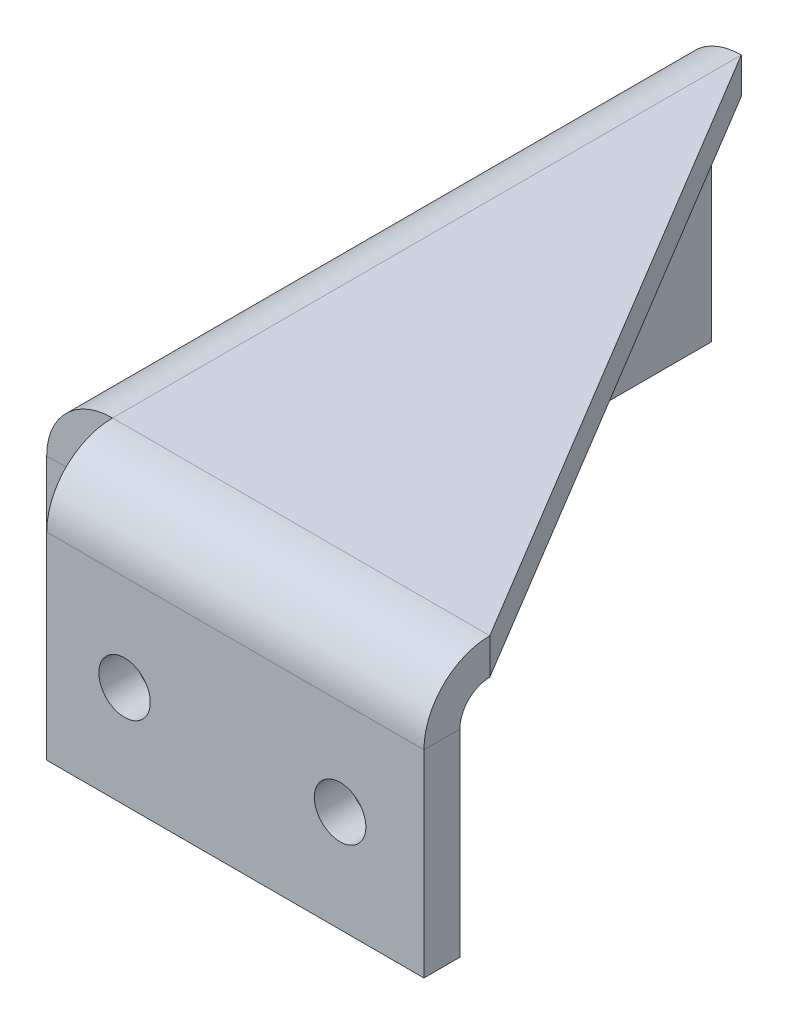
SolidWorks part; units mm, degrees
note: The reader was unsure of these and kept them because the rebuilt part matched: flange length of "Edge-Flange1", "Edge-Flange2".
material "1060 Alloy"
ref_plane "Front Plane" through (0, 0, 0) normal (0, 0, 1) x (1, 0, 0)
ref_plane "Top Plane" through (0, 0, 0) normal (0, 1, 0) x (1, 0, 0)
ref_plane "Right Plane" through (0, 0, 0) normal (1, 0, 0) x (0, 0, -1)
sketch "Sketch1" plane through (0, 0, 0) normal (0, 1, 0) x (1, 0, 0)
  line L1 (0, 0) -> (-31.5, 0)
  line L2 (0, 0) -> (0, 52.5)
  line L3 (0, 52.5) -> (-31.5, 52.5)
  line L4 (-31.5, 0) -> (-31.5, 52.5)
  dimension "D1" = 52.5
  dimension "D2" = 31.5
base flange "Base-Flange1" sketch "Sketch1" thickness 3 reverse thickness direction no parameters "D1"=0.7366
edge flange "Edge-Flange1" sketch "Sketch8" flange angle 90 flange length 22 flange position bend outside bend radius 2.5 thickness 3 relief rectangular parameters "D6"=10
sketch "Sketch8" plane through (0, -3, 0) normal (0, 0, -1) x (1, 0, 0)
  line L0 (0, 0) -> (-31.5, 0) construction
  line L1 (0, 0) -> (-31.5, 0)
  line L2 (-31.5, 0) -> (-31.5, 19)
  line L3 (-31.5, 19) -> (0, 19)
  line L4 (0, 19) -> (0, 0)
bend "EdgeBend1" bend radius 2.5 bend angle 90 parameters "D5"=1
edge flange "Edge-Flange2" sketch "Sketch11" flange angle 90 flange length 22 flange position bend outside bend radius 2.5 thickness 3 relief rectangular parameters "D6"=10
sketch "Sketch11" plane through (-31.5, -3, 0) normal (1, 0, 0) x (0, 0, 1)
  line L1 (0, 0) -> (-52.5, 0) construction
  line L2 (-52.5, 0) -> (-52.5, 19)
  line L3 (-52.5, 19) -> (0, 19)
  line L4 (0, 19) -> (0, 0)
  line L5 (0, 0) -> (-52.5, 0)
bend "EdgeBend2" bend radius 2.5 bend angle 90 parameters "D5"=2
sketch "Sketch12" plane through (0, 0, 0) normal (0, 1, 0) x (1, 0, 0)
  line L0 (-31.5, 52.5) -> (0, 0)
  line L1 (0, 0) -> (0, 52.5)
  line L2 (0, 52.5) -> (-31.5, 52.5)
extrude "Cut-Extrude1" cut sketch "Sketch12" against normal blind 10 normal cut yes
hole_wizard "M4 Clearance Hole1" positions "Sketch14" profile "Sketch13" hole size "M4" standard "ISO" end condition through all
sketch "Sketch14" plane through (0, 0, 2.5) normal (0, 0, -1) x (-1, 0, 0)
  line L2 (0, -22) -> (31.5, -22) construction
  line L5 (0, -5.5) -> (0, -22) construction
  point P0 (7, -13.5)
  point P7 (25, -13.5)
  dimension "D1" = 8.5
  dimension "D2" = 7
  dimension "D3" = 18
  dimension "D4" = 8.5
sketch "Sketch13" plane through (-7, -13.5, 2.5) normal (1, 0, 0) x (0, 1, 0)
  line L0 (0, 0) -> (0, 3)
  line L1 (0, 3) -> (2.15, 3)
  line L2 (2.15, 3) -> (2.15, 0)
  line L5 (2.15, 0) -> (0, 0)
  line L11 (0, -6.35) -> (0, 107.95) construction
  dimension "Thru Hole Dia." = 4.3
  dimension "Thru Hole Depth" = 3
hole_wizard "M4 Clearance Hole2" positions "Sketch16" profile "Sketch15" hole size "M4" standard "ISO" end condition through all
sketch "Sketch16" plane through (-34, 0, 0) normal (1, 0, 0) x (0, 0, -1)
  line L4 (0, -22) -> (52.5, -22) construction
  line L5 (52.5, -22) -> (52.5, -5.5) construction
  point P0 (44.5, -13.5)
  point P7 (8.5, -13.5)
  dimension "D1" = 8.5
  dimension "D2" = 8.5
  dimension "D3" = 36
  dimension "D4" = 8
sketch "Sketch15" plane through (-34, -13.5, -44.5) normal (0, 1, 0) x (0, 0, -1)
  line L0 (0, 0) -> (0, 3)
  line L1 (0, 3) -> (2.15, 3)
  line L2 (2.15, 3) -> (2.15, 0)
  line L5 (2.15, 0) -> (0, 0)
  line L11 (0, -6.35) -> (0, 107.95) construction
  dimension "Thru Hole Dia." = 4.3
  dimension "Thru Hole Depth" = 3
sketch "Bend-Lines1" [suppressed] plane through (0, 0, 0) normal (0, 1, 0) x (1, 0, 0)
sketch "Bounding-Box1" [suppressed] plane through (0, 0, 0) normal (0, 1, 0) x (1, 0, 0)
sheet metal parameters "Sheet-Metal1" thickness 3 parameters "D1"=0.7366
flat pattern "Flat-Pattern1" [suppressed]
sketch "Bend-Lines2" plane through (0, 0, 0) normal (0, 1, 0) x (1, 0, 0)
sketch3d "Bounding-Box2" [suppressed]
  line L0 (-31.5, 52.5, 0) -> (-31.5, 0, 0) construction
  line L1 (0, 52.5, 0) -> (0, 0, 0) construction
  line L2 (-31.5, 52.5, 0) -> (0, 52.5, 0) construction
  line L3 (-31.5, 0, 0) -> (0, 0, 0) construction
sheet metal parameters "Sheet-Metal2" thickness 3 parameters "D1"=0.7366
flat pattern "Flat-Pattern1"
sketch "Bend-Lines2" plane through (0, 0, 0) normal (0, 1, 0) x (1, 0, 0)
  line L0 (-31.5, -0.9635) -> (0, -0.9635) construction
  line L1 (-31.5, -0.9635) -> (0, -0.9635) construction
sketch3d "Bounding-Box2" [suppressed]
  line L0 (-31.5, 52.5, 0) -> (-31.5, -20.927, 0) construction
  line L1 (0, 52.5, 0) -> (0, -20.927, 0) construction
  line L2 (-31.5, 52.5, 0) -> (0, 52.5, 0) construction
  line L3 (-31.5, -20.927, 0) -> (0, -20.927, 0) construction
bend of the flat pattern "Flatten-<EdgeBend1>1"
sheet metal parameters "Sheet-Metal3" thickness 3 parameters "D1"=0.7366
flat pattern "Flat-Pattern1"
sketch "Bend-Lines2" plane through (0, 0, 0) normal (0, 1, 0) x (1, 0, 0)
  line L0 (-31.5, -1.9635) -> (0, -1.9635) construction
  line L1 (-31.5, -1.9635) -> (0, -1.9635) construction
  line L2 (-33.4635, 52.5) -> (-33.4635, 0) construction
  line L3 (-33.4635, 52.5) -> (-33.4635, 0) construction
sketch3d "Bounding-Box2" [suppressed]
  line L0 (-53.427, 52.5, 0) -> (-53.427, -21.927, 0) construction
  line L1 (0, 52.5, 0) -> (0, -21.927, 0) construction
  line L2 (-53.427, 52.5, 0) -> (0, 52.5, 0) construction
  line L3 (-53.427, -21.927, 0) -> (0, -21.927, 0) construction
bend of the flat pattern "Flatten-<EdgeBend1>1"
bend of the flat pattern "Flatten-<EdgeBend2>1"
sheet metal parameters "Sheet-Metal4" thickness 3 parameters "D1"=0.7366
flat pattern "Flat-Pattern1"
sketch "Bend-Lines2" plane through (0, 0, 0) normal (0, 1, 0) x (1, 0, 0)
  line L0 (-31.5, -1.9635) -> (0, -1.9635) construction
  line L1 (-31.5, -1.9635) -> (0, -1.9635) construction
  line L2 (-33.4635, 52.5) -> (-33.4635, 0) construction
  line L3 (-33.4635, 52.5) -> (-33.4635, 0) construction
sketch3d "Bounding-Box2" [suppressed]
  line L0 (-53.427, 52.5, 0) -> (-53.427, -21.927, 0) construction
  line L1 (0, 52.5, 0) -> (0, -21.927, 0) construction
  line L2 (-53.427, 52.5, 0) -> (0, 52.5, 0) construction
  line L3 (-53.427, -21.927, 0) -> (0, -21.927, 0) construction
bend of the flat pattern "Flatten-<EdgeBend1>1"
bend of the flat pattern "Flatten-<EdgeBend2>1"
sheet metal parameters "Sheet-Metal5" thickness 3 parameters "D1"=0.7366
flat pattern "Flat-Pattern1"
sketch "Bend-Lines2" plane through (0, 0, 0) normal (0, 1, 0) x (1, 0, 0)
  line L0 (-31.5, -1.9635) -> (0, -1.9635) construction
  line L1 (-31.5, -1.9635) -> (0, -1.9635) construction
  line L2 (-33.4635, 52.5) -> (-33.4635, 0) construction
  line L3 (-33.4635, 52.5) -> (-33.4635, 0) construction
sketch3d "Bounding-Box2" [suppressed]
  line L0 (-53.427, 52.5, 0) -> (-53.427, -21.927, 0) construction
  line L1 (0, 52.5, 0) -> (0, -21.927, 0) construction
  line L2 (-53.427, 52.5, 0) -> (0, 52.5, 0) construction
  line L3 (-53.427, -21.927, 0) -> (0, -21.927, 0) construction
bend of the flat pattern "Flatten-<EdgeBend1>1"
bend of the flat pattern "Flatten-<EdgeBend2>1"
sheet metal parameters "Sheet-Metal6" thickness 3 parameters "D1"=0.7366
flat pattern "Flat-Pattern1"
sketch "Bend-Lines2" plane through (0, 0, 0) normal (0, 1, 0) x (1, 0, 0)
  line L0 (-31.5, -3.1416) -> (0, -3.1416) construction
  line L1 (-31.5, -3.1416) -> (0, -3.1416) construction
  line L2 (-34.6416, 52.5) -> (-34.6416, 0) construction
  line L3 (-34.6416, 52.5) -> (-34.6416, 0) construction
sketch3d "Bounding-Box2" [suppressed]
  line L0 (-54.2832, 52.5, 0) -> (-54.2832, -22.7832, 0) construction
  line L1 (0, 52.5, 0) -> (0, -22.7832, 0) construction
  line L2 (-54.2832, 52.5, 0) -> (0, 52.5, 0) construction
  line L3 (-54.2832, -22.7832, 0) -> (0, -22.7832, 0) construction
bend of the flat pattern "Flatten-<EdgeBend1>1"
bend of the flat pattern "Flatten-<EdgeBend2>1"
